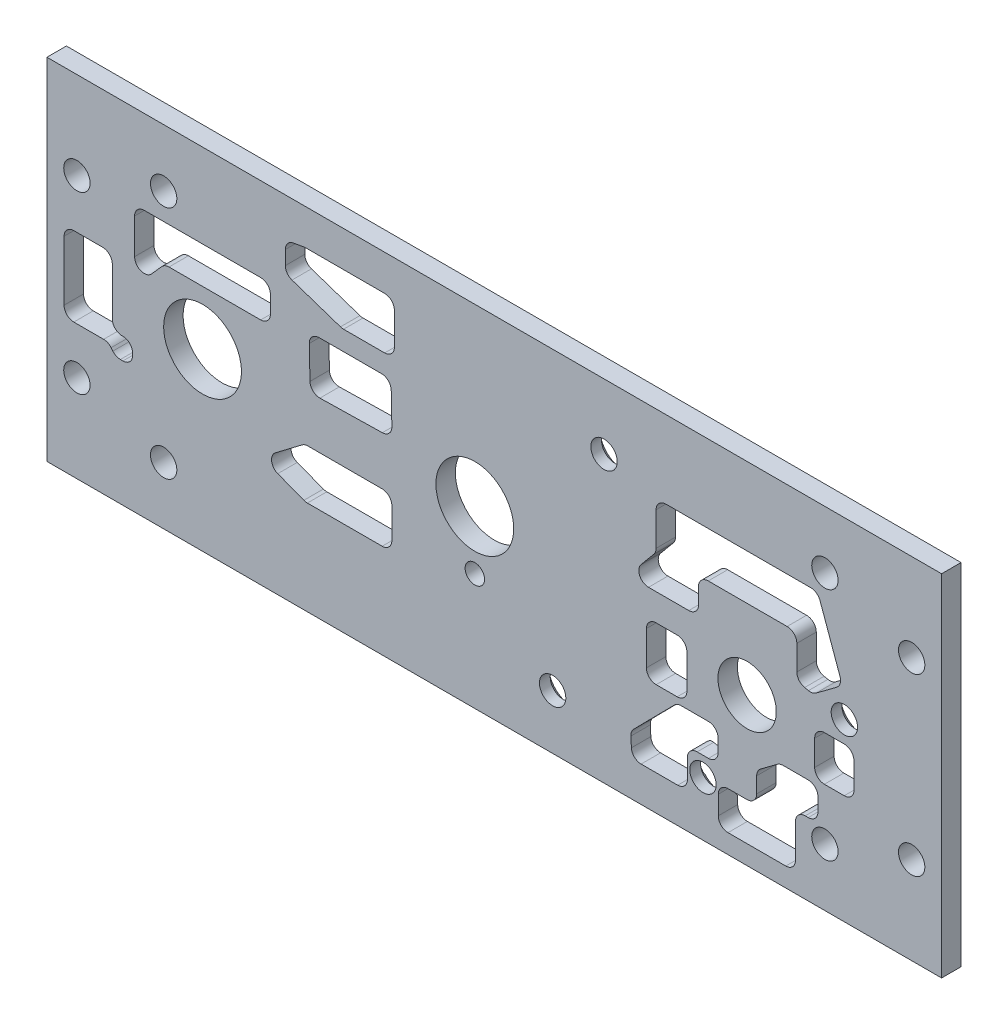
SolidWorks part; units mm, degrees
ref_plane "Front Plane" through (0, 0, 0) normal (0, 0, 1) x (1, 0, 0)
ref_plane "Top Plane" through (0, 0, 0) normal (0, 1, 0) x (1, 0, 0)
ref_plane "Right Plane" through (0, 0, 0) normal (1, 0, 0) x (0, 0, -1)
sketch "Sketch1" plane through (0, 0, 0) normal (0, 0, 1) x (1, 0, 0)
  line L4 (0, 57.15) -> (-146.05, 57.15)
  line L5 (-146.05, 57.15) -> (-146.05, 0)
  line L6 (-146.05, 0) -> (0, 0)
  line L7 (0, 0) -> (0, 57.15)
  line L8 (0, 57.15) -> (-146.05, 57.15)
  line L9 (-146.05, 57.15) -> (-146.05, 0)
  line L10 (-146.05, 0) -> (0, 0)
  line L11 (0, 0) -> (0, 57.15)
  dimension "D1" = 0
extrude "Boss-Extrude1" add sketch "Sketch1" against normal blind 3.175
hole_wizard "#6 Clearance Hole1" positions "Sketch3" profile "Sketch2" hole size "#6" standard "ANSI Inch" end condition through all
sketch "Sketch3" plane through (0, 0, -3.175) normal (0, 0, -1) x (-1, 0, 0)
  point P0 (4.8895, 42.8625)
  point P3 (141.1605, 42.8625)
  point P6 (141.1605, 14.2875)
  point P9 (4.8895, 14.2875)
  point P12 (19.05, 47.752)
  point P15 (19.05, 9.398)
  point P18 (127, 9.398)
  point P21 (127, 47.752)
sketch "Sketch2" plane through (-4.8895, 42.8625, -3.175) normal (1, 0, 0) x (0, 1, 0)
  line L0 (0, 0) -> (0, 3.175)
  line L1 (0, 3.175) -> (2.1526, 3.175)
  line L2 (2.1526, 3.175) -> (2.1526, 0)
  line L5 (2.1526, 0) -> (0, 0)
  line L11 (0, -6.35) -> (0, 107.95) construction
  dimension "Thru Hole Dia." = 4.3053
  dimension "Thru Hole Depth" = 3.175
hole_wizard "1/2 (0.5) Diameter Hole1" positions "Sketch5" profile "Sketch4" hole size "1/2" standard "ANSI Inch" end condition through all
sketch "Sketch5" plane through (0, 0, -3.175) normal (0, 0, -1) x (-1, 0, 0)
  point P0 (76.2, 28.575)
  point P3 (120.65, 28.575)
sketch "Sketch4" plane through (-76.2, 28.575, -3.175) normal (1, 0, 0) x (0, 1, 0)
  line L0 (0, 0) -> (0, 3.175)
  line L1 (0, 3.175) -> (6.35, 3.175)
  line L2 (6.35, 3.175) -> (6.35, 0)
  line L5 (6.35, 0) -> (0, 0)
  line L11 (0, -6.35) -> (0, 107.95) construction
  dimension "Thru Hole Dia." = 12.7
  dimension "Thru Hole Depth" = 3.175
hole_wizard "3/8 (0.375) Diameter Hole1" positions "Sketch7" profile "Sketch6" hole size "3/8" standard "ANSI Inch" end condition through all
sketch "Sketch7" plane through (0, 0, -3.175) normal (0, 0, -1) x (-1, 0, 0)
  point P0 (31.75, 24.13)
sketch "Sketch6" plane through (-31.75, 24.13, -3.175) normal (1, 0, 0) x (0, 1, 0)
  line L0 (0, 0) -> (0, 3.175)
  line L1 (0, 3.175) -> (4.7625, 3.175)
  line L2 (4.7625, 3.175) -> (4.7625, 0)
  line L5 (4.7625, 0) -> (0, 0)
  line L11 (0, -6.35) -> (0, 107.95) construction
  dimension "Thru Hole Dia." = 9.525
  dimension "Thru Hole Depth" = 3.175
hole_wizard "1/8 (0.125) Diameter Hole1" positions "Sketch9" profile "Sketch8" hole size "1/8" standard "ANSI Inch" end condition through all
sketch "Sketch9" plane through (0, 0, -3.175) normal (0, 0, -1) x (-1, 0, 0)
  point P0 (76.2, 19.05)
sketch "Sketch8" plane through (-76.2, 19.05, -3.175) normal (1, 0, 0) x (0, 1, 0)
  line L0 (0, 0) -> (0, 3.175)
  line L1 (0, 3.175) -> (1.5875, 3.175)
  line L2 (1.5875, 3.175) -> (1.5875, 0)
  line L5 (1.5875, 0) -> (0, 0)
  line L11 (0, -6.35) -> (0, 107.95) construction
  dimension "Thru Hole Dia." = 3.175
  dimension "Thru Hole Depth" = 3.175
hole_wizard "CSK for #6 Flat Head Machine Screw (100)2" positions "Sketch13" profile "Sketch14" countersink size "#6" standard "ANSI Inch" end condition through all
sketch "Sketch13" plane through (0, 0, -3.175) normal (0, 0, -1) x (-1, 0, 0)
  point P0 (63.5, 8.89)
  point P2 (55.108, 46.4933)
  point P4 (15.875, 28.58)
  point P6 (38.95, 8.89)
sketch "Sketch14" plane through (-63.5, 8.89, -3.175) normal (1, 0, 0) x (0, 1, 0)
  line L0 (0, 0) -> (0, 3.175)
  line L1 (0, 3.175) -> (2.1526, 3.175)
  line L2 (2.1526, 3.175) -> (2.1526, 1.4209)
  line L3 (2.1526, 1.4209) -> (3.846, 0)
  line L5 (3.846, 0) -> (0, 0)
  line L6 (-2.1526, 1.4209) -> (-3.846, 0) construction
  line L11 (0, -6.35) -> (0, 107.95) construction
  dimension "Thru Hole Dia." = 4.3053
  dimension "Thru Hole Depth" = 3.175
  dimension "Near C'Sink Dia." = 7.692
  dimension "Near C'Sink Angle" = 100
sketch "Sketch15" plane through (0, 0, -3.175) normal (0, 0, -1) x (-1, 0, 0)
  line L0 (21.3472, 44.4967) -> (45.0121, 44.4967)
  line L1 (46.5996, 42.9092) -> (46.5996, 37.4558)
  line L2 (46.9673, 36.4398) -> (49.0674, 33.9182)
  line L3 (47.8475, 31.3147) -> (41.2725, 31.3147)
  line L4 (39.685, 32.9022) -> (39.685, 35.5002)
  line L5 (38.0975, 37.0877) -> (25.2199, 37.0877)
  line L6 (23.6324, 35.5002) -> (23.6324, 31.4465)
  line L7 (22.3581, 29.8902) -> (21.7351, 29.7648)
  line L8 (20.4716, 30.0495) -> (17.1327, 32.5446)
  line L9 (16.5889, 34.3526) -> (19.853, 43.4456)
  line L10 (43.1694, 26.9041) -> (46.5996, 26.9041)
  line L11 (48.1871, 25.3166) -> (48.1871, 19.7591)
  line L12 (46.5996, 18.1716) -> (43.1694, 18.1716)
  line L13 (41.5819, 19.7591) -> (41.5819, 25.3166)
  line L14 (90.921, 42.9092) -> (97.6271, 42.9092)
  line L15 (98.1323, 42.9918) -> (106.0507, 45.6499)
  line L16 (107.133, 47.1549) -> (107.133, 49.4288)
  line L17 (105.8312, 50.9904) -> (104.1288, 51.3019)
  line L18 (103.8431, 51.3278) -> (90.921, 51.3278)
  line L19 (89.3335, 49.7403) -> (89.3335, 44.4967)
  line L20 (103.2202, 38.1053) -> (103.1126, 32.7901)
  line L21 (101.4933, 31.235) -> (91.2976, 31.4416)
  line L22 (89.7426, 33.0609) -> (89.8461, 38.1696)
  line L23 (91.4333, 39.725) -> (101.6331, 39.725)
  line L24 (111.1606, 37.4558) -> (126.1275, 37.4558)
  line L25 (127.3155, 36.9213) -> (128.968, 35.057)
  line L26 (131.7435, 36.11) -> (131.7435, 41.8581)
  line L27 (130.156, 43.4456) -> (111.1606, 43.4456)
  line L28 (109.5731, 41.8581) -> (109.5731, 39.0433)
  line L29 (143.2554, 33.2422) -> (143.2554, 23.4881)
  line L30 (141.6679, 21.9006) -> (136.7909, 21.9006)
  line L31 (135.5705, 21.3285) -> (135.2847, 20.9849)
  line L32 (134.0643, 20.4128) -> (133.6479, 20.4128)
  line L33 (132.0604, 22.0003) -> (132.0604, 22.3105)
  line L34 (133.6479, 23.898) -> (133.7923, 23.898)
  line L35 (135.3798, 25.4855) -> (135.3798, 33.2422)
  line L36 (136.9673, 34.8297) -> (141.6679, 34.8297)
  line L37 (91.3301, 23.4881) -> (103.4436, 23.4881)
  line L38 (104.4023, 23.1659) -> (108.758, 19.8657)
  line L39 (108.3673, 17.118) -> (104.1062, 15.4853)
  line L40 (103.5382, 15.3802) -> (91.3301, 15.3802)
  line L41 (89.7426, 16.9677) -> (89.7426, 21.9006)
  line L42 (15.8936, 25.1311) -> (19.134, 25.1311)
  line L43 (20.7215, 23.5436) -> (20.7215, 19.4102)
  line L44 (19.134, 17.8227) -> (15.8936, 17.8227)
  line L45 (14.3061, 19.4102) -> (14.3061, 23.5436)
  line L46 (20.1879, 15.5305) -> (20.1879, 13.3812)
  line L47 (21.7754, 11.7937) -> (22.2638, 11.7937)
  line L48 (23.8513, 10.2062) -> (23.8513, 4.7003)
  line L49 (25.4388, 3.1128) -> (34.8743, 3.1128)
  line L50 (36.4618, 4.7003) -> (36.4618, 7.7524)
  line L52 (25.8742, 17.118) -> (21.7754, 17.118)
  line L53 (36.4835, 15.651) -> (36.4835, 13.6067)
  line L54 (38.071, 12.0192) -> (39.9092, 12.0192)
  line L55 (41.4967, 10.4317) -> (41.4967, 7.3058)
  line L56 (43.0842, 5.7183) -> (49.0555, 5.7183)
  line L57 (50.6408, 7.2234) -> (50.725, 8.8432)
  line L58 (50.2698, 10.0404) -> (43.6356, 16.7658)
  line L59 (42.5054, 17.2385) -> (38.071, 17.2385)
  line L60 (26.825, 16.8018) -> (29.5567, 14.759)
  line L61 (30.1935, 13.4877) -> (30.1935, 10.9274)
  line L62 (31.781, 9.3399) -> (34.8743, 9.3399)
  arc A0 (17.1327, 32.5446) -> (16.5889, 34.3526) centre (18.083, 33.8163) cw
  arc A1 (21.3472, 44.4967) -> (19.853, 43.4456) centre (21.3472, 42.9092) ccw
  arc A2 (45.0121, 44.4967) -> (46.5996, 42.9092) centre (45.0121, 42.9092) cw
  arc A3 (46.5996, 37.4558) -> (46.9673, 36.4398) centre (48.1871, 37.4558) ccw
  arc A4 (49.0674, 33.9182) -> (47.8475, 31.3147) centre (47.8475, 32.9022) cw
  arc A5 (41.2725, 31.3147) -> (39.685, 32.9022) centre (41.2725, 32.9022) cw
  arc A6 (39.685, 35.5002) -> (38.0975, 37.0877) centre (38.0975, 35.5002) ccw
  arc A7 (25.2199, 37.0877) -> (23.6324, 35.5002) centre (25.2199, 35.5002) ccw
  arc A8 (23.6324, 31.4465) -> (22.3581, 29.8902) centre (22.0449, 31.4465) cw
  arc A9 (21.7351, 29.7648) -> (20.4716, 30.0495) centre (21.4219, 31.3211) cw
  arc A10 (43.1694, 26.9041) -> (41.5819, 25.3166) centre (43.1694, 25.3166) ccw
  arc A11 (46.5996, 26.9041) -> (48.1871, 25.3166) centre (46.5996, 25.3166) cw
  arc A12 (48.1871, 19.7591) -> (46.5996, 18.1716) centre (46.5996, 19.7591) cw
  arc A13 (43.1694, 18.1716) -> (41.5819, 19.7591) centre (43.1694, 19.7591) cw
  arc A14 (104.1288, 51.3019) -> (103.8431, 51.3278) centre (103.8431, 49.7403) ccw
  arc A15 (107.133, 49.4288) -> (105.8312, 50.9904) centre (105.5455, 49.4288) ccw
  arc A16 (106.0507, 45.6499) -> (107.133, 47.1549) centre (105.5455, 47.1549) ccw
  arc A17 (97.6271, 42.9092) -> (98.1323, 42.9918) centre (97.6271, 44.4967) ccw
  arc A18 (90.921, 51.3278) -> (89.3335, 49.7403) centre (90.921, 49.7403) ccw
  arc A19 (90.921, 42.9092) -> (89.3335, 44.4967) centre (90.921, 44.4967) cw
  arc A20 (89.8461, 38.1696) -> (91.4333, 39.725) centre (91.4333, 38.1375) cw
  arc A21 (91.2976, 31.4416) -> (89.7426, 33.0609) centre (91.3298, 33.0287) cw
  arc A22 (103.1126, 32.7901) -> (101.4933, 31.235) centre (101.5254, 32.8222) cw
  arc A23 (103.2202, 38.1053) -> (101.6331, 39.725) centre (101.6331, 38.1375) ccw
  arc A24 (131.7435, 41.8581) -> (130.156, 43.4456) centre (130.156, 41.8581) ccw
  arc A25 (128.968, 35.057) -> (131.7435, 36.11) centre (130.156, 36.11) ccw
  arc A26 (126.1275, 37.4558) -> (127.3155, 36.9213) centre (126.1275, 35.8683) cw
  arc A27 (111.1606, 37.4558) -> (109.5731, 39.0433) centre (111.1606, 39.0433) cw
  arc A28 (111.1606, 43.4456) -> (109.5731, 41.8581) centre (111.1606, 41.8581) ccw
  arc A29 (143.2554, 23.4881) -> (141.6679, 21.9006) centre (141.6679, 23.4881) cw
  arc A30 (136.7909, 21.9006) -> (135.5705, 21.3285) centre (136.7909, 20.3131) ccw
  arc A31 (135.2847, 20.9849) -> (134.0643, 20.4128) centre (134.0643, 22.0003) cw
  arc A32 (133.6479, 20.4128) -> (132.0604, 22.0003) centre (133.6479, 22.0003) cw
  arc A33 (132.0604, 22.3105) -> (133.6479, 23.898) centre (133.6479, 22.3105) cw
  arc A34 (133.7923, 23.898) -> (135.3798, 25.4855) centre (133.7923, 25.4855) ccw
  arc A35 (135.3798, 33.2422) -> (136.9673, 34.8297) centre (136.9673, 33.2422) cw
  arc A36 (143.2554, 33.2422) -> (141.6679, 34.8297) centre (141.6679, 33.2422) ccw
  arc A37 (91.3301, 15.3802) -> (89.7426, 16.9677) centre (91.3301, 16.9677) cw
  arc A38 (104.1062, 15.4853) -> (103.5382, 15.3802) centre (103.5382, 16.9677) cw
  arc A39 (108.758, 19.8657) -> (108.3673, 17.118) centre (107.7992, 18.6004) cw
  arc A40 (103.4436, 23.4881) -> (104.4023, 23.1659) centre (103.4436, 21.9006) cw
  arc A41 (91.3301, 23.4881) -> (89.7426, 21.9006) centre (91.3301, 21.9006) ccw
  arc A42 (15.8936, 17.8227) -> (14.3061, 19.4102) centre (15.8936, 19.4102) cw
  arc A43 (20.7215, 19.4102) -> (19.134, 17.8227) centre (19.134, 19.4102) cw
  arc A44 (19.134, 25.1311) -> (20.7215, 23.5436) centre (19.134, 23.5436) cw
  arc A45 (15.8936, 25.1311) -> (14.3061, 23.5436) centre (15.8936, 23.5436) ccw
  arc A47 (34.8743, 3.1128) -> (36.4618, 4.7003) centre (34.8743, 4.7003) ccw
  arc A48 (23.8513, 4.7003) -> (25.4388, 3.1128) centre (25.4388, 4.7003) ccw
  arc A49 (20.1879, 13.3812) -> (21.7754, 11.7937) centre (21.7754, 13.3812) ccw
  arc A51 (20.1879, 15.5305) -> (21.7754, 17.118) centre (21.7754, 15.5305) cw
  arc A52 (22.2638, 11.7937) -> (23.8513, 10.2062) centre (22.2638, 10.2062) cw
  arc A53 (25.8742, 17.118) -> (26.825, 16.8018) centre (25.8742, 15.5305) cw
  arc A54 (50.725, 8.8432) -> (50.2698, 10.0404) centre (49.1397, 8.9256) ccw
  arc A55 (49.0555, 5.7183) -> (50.6408, 7.2234) centre (49.0555, 7.3058) ccw
  arc A56 (41.4967, 7.3058) -> (43.0842, 5.7183) centre (43.0842, 7.3058) ccw
  arc A57 (39.9092, 12.0192) -> (41.4967, 10.4317) centre (39.9092, 10.4317) cw
  arc A58 (36.4835, 13.6067) -> (38.071, 12.0192) centre (38.071, 13.6067) ccw
  arc A59 (43.6356, 16.7658) -> (42.5054, 17.2385) centre (42.5054, 15.651) ccw
  arc A60 (36.4835, 15.651) -> (38.071, 17.2385) centre (38.071, 15.651) cw
  arc A61 (29.5567, 14.759) -> (30.1935, 13.4877) centre (28.606, 13.4877) cw
  arc A62 (30.1935, 10.9274) -> (31.781, 9.3399) centre (31.781, 10.9274) ccw
  arc A63 (36.4618, 7.7524) -> (34.8743, 9.3399) centre (34.8743, 7.7524) ccw
  dimension "D1" = 1.5875
  dimension "D2" = 1.5875
  dimension "D3" = 1.5875
  dimension "D4" = 1.5875
  dimension "D5" = 1.5875
  dimension "D6" = 1.5875
  dimension "D7" = 1.5875
  dimension "D8" = 1.5875
  dimension "D9" = 1.5875
  dimension "D10" = 1.5875
  dimension "D11" = 1.5875
extrude "Cut-Extrude1" cut sketch "Sketch15" against normal through all
